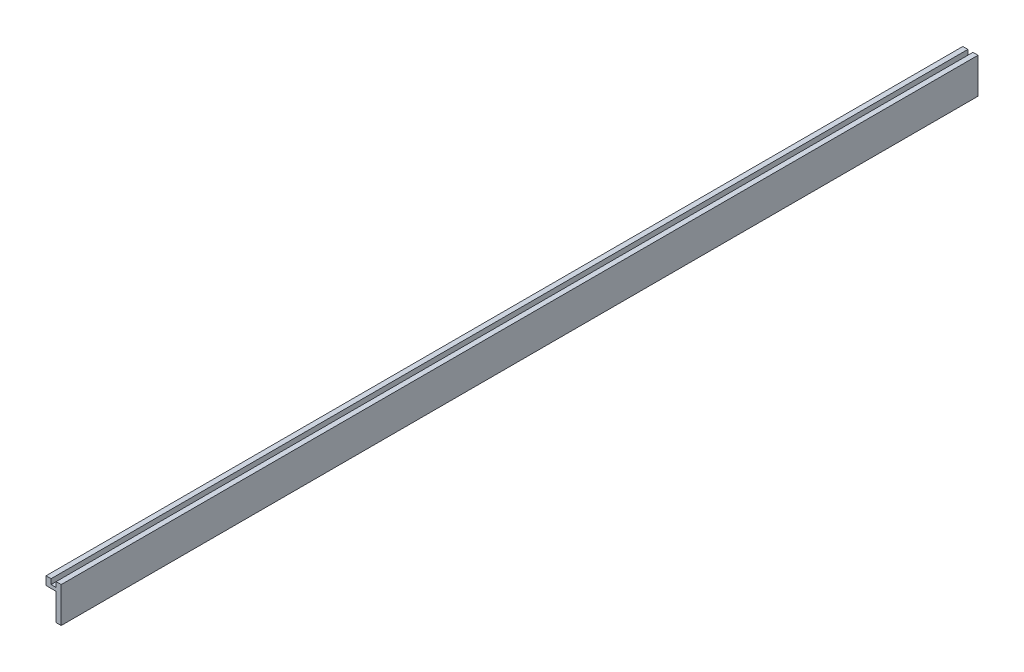
SolidWorks part; units mm, degrees
ref_plane "Front Plane" through (0, 0, 0) normal (0, 0, 1) x (1, 0, 0)
ref_plane "Top Plane" through (0, 0, 0) normal (0, 1, 0) x (1, 0, 0)
ref_plane "Right Plane" through (0, 0, 0) normal (1, 0, 0) x (0, 0, -1)
sketch "Sketch1" plane through (0, 0, 0) normal (0, 0, 1) x (1, 0, 0)
  line L0 (0, 35) -> (5, 35)
  line L1 (0, 0) -> (15, 0)
  line L2 (0, 0) -> (0, 35)
  line L4 (15, 0) -> (15, 35)
  line L5 (5, 35) -> (5, 30)
  line L6 (5, 30) -> (10, 30)
  line L7 (10, 30) -> (10, 35)
  line L8 (10, 35) -> (15, 35)
  dimension "D1" = 15
  dimension "D2" = 35
  dimension "D3" = 5
  dimension "D4" = 5
extrude "Boss-Extrude1" add sketch "Sketch1" along normal blind 904
sketch "Sketch4" plane through (0, 0, 0) normal (-1, 0, 0) x (0, 0, 1)
  line L0 (0, 35) -> (0, 0) construction
  line L1 (0, 26.6744) -> (904, 26.6744)
  line L2 (0, 26.6744) -> (0, 0)
  line L3 (0, 0) -> (904, 0)
  line L4 (904, 26.6744) -> (904, 0)
extrude "Cut-Extrude3" cut sketch "Sketch4" against normal blind 10
sketch "Sketch7" plane through (10, 0, 0) normal (-1, 0, 0) x (0, 0, 1)
  line L0 (0, 0) -> (904, 0) construction
  line L1 (904, 0) -> (904, 26.6744) construction
  circle A0 centre (304, 12.5) radius 5
  dimension "D1" = 12.5
  dimension "D2" = 10
  dimension "D3" = 600
extrude "Boss-Extrude4" add sketch "Sketch7" along normal blind 5
